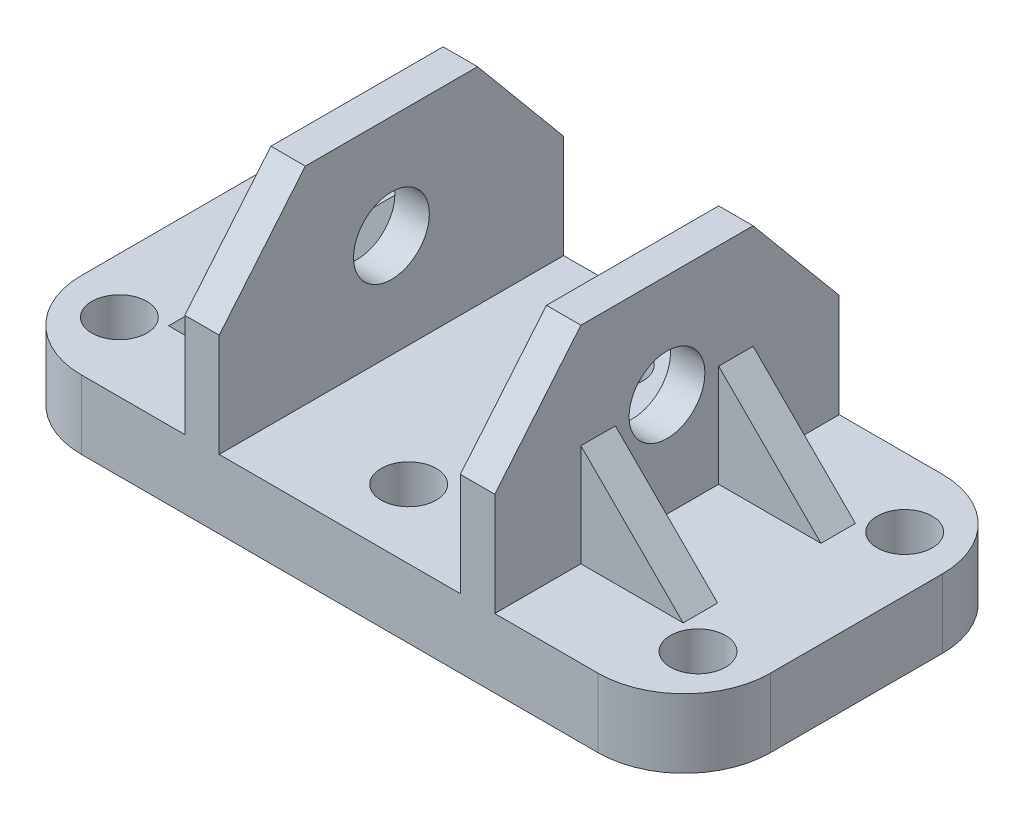
SolidWorks part; units mm, degrees
ref_plane "Front Plane" through (0, 0, 0) normal (0, 0, 1) x (1, 0, 0)
ref_plane "Top Plane" through (0, 0, 0) normal (0, 1, 0) x (1, 0, 0)
ref_plane "Right Plane" through (0, 0, 0) normal (1, 0, 0) x (0, 0, -1)
sketch "Sketch2" plane through (0, 0, 0) normal (0, 1, 0) x (1, 0, 0)
  line L1 (-100, 50) -> (100, 50)
  line L2 (-100, 50) -> (-100, -50)
  line L3 (-100, -50) -> (100, -50)
  line L4 (100, 50) -> (100, -50)
  line L5 (-100, 50) -> (100, -50) construction
  line L6 (-100, -50) -> (100, 50) construction
  point P0 (0, 0)
  dimension "D1" = 200
  dimension "D2" = 100
extrude "Boss-Extrude1" add sketch "Sketch2" along normal blind 20
fillet "Fillet1" radius 25 4 edges at (-100, 10, 50) (-100, 10, -50) (100, 10, -50) (100, 10, 50)
sketch "Sketch3" plane through (0, 20, 0) normal (0, 1, 0) x (1, 0, 0)
  line L0 (-108.5295, 0) -> (119.7364, 0) construction
  line L1 (0, 11.9598) -> (0, -71.9598) construction
  line L2 (-84, 45.0619) -> (-84, -41.7454) construction
  line L5 (84, 47.2925) -> (84, -45.4631) construction
  line L6 (-99.4283, 30) -> (-58.534, 30) construction
  line L7 (61.3223, 30) -> (100.3577, 30) construction
  line L8 (-96.4542, -30) -> (-67.6548, -30) construction
  line L9 (64.4823, -30) -> (100.3577, -30) construction
  line L10 (75, 50) -> (-75, 50) construction
  line L11 (-75, -50) -> (75, -50) construction
  circle A0 centre (-84, -30) radius 8
  circle A1 centre (84, -30) radius 8
  circle A2 centre (84, 30) radius 8
  circle A3 centre (-84, 30) radius 8
  circle A4 centre (0, -30) radius 8
  circle A5 centre (0, 30) radius 8
  point P16 (-40, 0)
  dimension "D1" = 16
  dimension "D2" = 16
  dimension "D3" = 16
  dimension "D4" = 16
  dimension "D5" = 84
  dimension "D11" = 16
  dimension "D14" = 16
  dimension "D6" = 84
  dimension "D7" = 20
  dimension "D8" = 20
  dimension "D9" = 20
  dimension "D10" = 20
  dimension "D15" = 20
  dimension "D16" = 20
  dimension "D17" = 84
extrude "Cut-Extrude2" cut sketch "Sketch3" against normal blind 20
sketch "Sketch4" plane through (0, 0, 0) normal (0, 1, 0) x (1, 0, 0)
  line L0 (-75, -50) -> (75, -50) construction
  line L1 (-45, 50) -> (-35, 50)
  line L2 (-45, 50) -> (-45, -50)
  line L3 (-45, -50) -> (-35, -50)
  line L4 (-35, 50) -> (-35, -50)
  line L5 (-45, 50) -> (-35, -50) construction
  line L6 (-45, -50) -> (-35, 50) construction
  line L7 (-100, 25) -> (-100, -25) construction
  line L8 (0, 60.1631) -> (0, -78.2514) construction
  line L9 (45, -50) -> (35, -50)
  line L10 (45, 50) -> (35, 50)
  line L11 (45, 50) -> (45, -50)
  line L12 (35, 50) -> (35, -50)
  point P0 (-40, 0)
  dimension "D1" = 10
  dimension "D2" = 55
extrude "Boss-Extrude3" add sketch "Sketch4" along normal blind 80
chamfer "Chamfer1" distance 30 distance2 25 4 edges at (40, 80, -50) (-40, 80, -50) (40, 80, 50) (-40, 80, 50) first distance on face at (0, 36.6667, -50) first distance on face at (0, 36.6667, 50)
sketch "Sketch5" plane through (45, 0, 0) normal (1, 0, 0) x (0, 0, -1)
  line L0 (-50, 50) -> (-50, 20) construction
  line L1 (-25, 80) -> (25, 80) construction
  circle A0 centre (0, 50) radius 11
  dimension "D1" = 22
  dimension "D2" = 50
  dimension "D3" = 30
extrude "Cut-Extrude3" cut sketch "Sketch5" against normal blind 127
sketch "Sketch8" plane through (0, 20, 0) normal (0, 1, 0) x (1, 0, 0)
  line L0 (45, 50) -> (45, -50) construction
  line L1 (45, -25) -> (75.6954, -25)
  line L2 (45, -25) -> (45, -15)
  line L3 (45, -15) -> (75.6954, -15)
  line L4 (75.6954, -25) -> (75.6954, -15)
  line L5 (45, -50) -> (75, -50) construction
  line L6 (110.4956, 0) -> (-129.3703, 0) construction
  line L7 (0, 62.3258) -> (0, -74.5157) construction
  line L8 (45, 15) -> (75.6954, 15)
  line L9 (75.6954, 25) -> (75.6954, 15)
  line L10 (45, 25) -> (75.6954, 25)
  line L11 (45, 25) -> (45, 15)
  line L12 (-45, -15) -> (-75.6954, -15)
  line L13 (-75.6954, -25) -> (-75.6954, -15)
  line L14 (-45, -25) -> (-75.6954, -25)
  line L15 (-45, -25) -> (-45, -15)
  line L16 (-45, 25) -> (-45, 15)
  line L17 (-45, 25) -> (-75.6954, 25)
  line L18 (-75.6954, 25) -> (-75.6954, 15)
  line L19 (-45, 15) -> (-75.6954, 15)
  dimension "D1" = 10
  dimension "D2" = 25
extrude "Boss-Extrude4" add sketch "Sketch8" along normal blind 30
chamfer "Chamfer2" distance 31 angle 45 4 edges at (-75.6954, 50, -20) (-75.6954, 50, 20) (75.6954, 50, -20) (75.6954, 50, 20)
